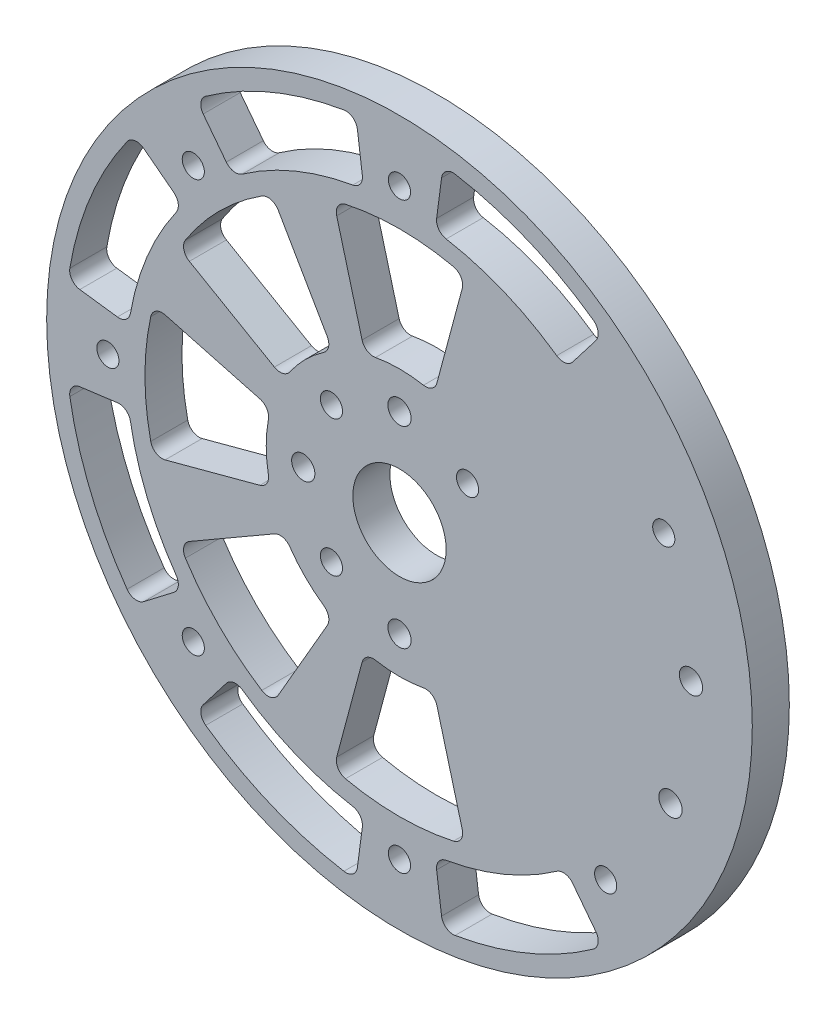
SolidWorks part; units mm, degrees
material "Balsa"
ref_plane "Front Plane" through (0, 0, 0) normal (0, 0, 1) x (1, 0, 0)
ref_plane "Top Plane" through (0, 0, 0) normal (0, 1, 0) x (1, 0, 0)
ref_plane "Right Plane" through (0, 0, 0) normal (1, 0, 0) x (0, 0, -1)
sketch "Sketch1" plane through (0, 0, 0) normal (0, 0, 1) x (1, 0, 0)
  line L0 (45.3154, 21.1309) -> (0, 0) construction
  line L1 (0, 0) -> (35.3553, -35.3553) construction
  line L2 (49.9788, 1.4542) -> (0, 0) construction
  line L3 (0, 0) -> (46.4674, -18.4603) construction
  circle A0 centre (45.3154, 21.1309) radius 1.8986
  circle A1 centre (49.9788, 1.4542) radius 1.9939
  circle A2 centre (0, 0) radius 60.5
  circle A3 centre (0, 0) radius 8
  circle A4 centre (0, 0) radius 16.5 construction
  circle A5 centre (46.4674, -18.4603) radius 1.9939
  circle A6 centre (0, 0) radius 50 construction
  circle A27 centre (0, -16.5) radius 1.9939
  circle A28 centre (11.6673, -11.6673) radius 1.8986 construction
  circle A30 centre (0, -50) radius 1.8986
  circle A31 centre (-16.5, 0) radius 1.9939
  circle A32 centre (-11.6673, -11.6673) radius 1.8986
  circle A33 centre (0, 16.5) radius 1.9939
  circle A34 centre (-11.6673, 11.6673) radius 1.8986
  circle A35 centre (16.5, 0) radius 1.9939 construction
  circle A36 centre (11.6673, 11.6673) radius 1.8986
  circle A38 centre (-35.3553, -35.3553) radius 1.8986
  circle A40 centre (-50, 0) radius 1.8986
  circle A42 centre (-35.3553, 35.3553) radius 1.8986
  circle A44 centre (0, 50) radius 1.8986
  circle A46 centre (35.3553, 35.3553) radius 1.8986 construction
  circle A48 centre (50, 0) radius 1.8986 construction
  circle A50 centre (35.3553, -35.3553) radius 1.8986
  dimension "D1" = 121
  dimension "D4" = 70
  dimension "D6" = 100
  dimension "D7" = 23.333
  dimension "D8" = 33
  dimension "D9" = 3.7973
  dimension "D10" = 3.9878
  dimension "D15" = 3.7973
  dimension "D17" = 3.9878
  dimension "D18" = 3.7973
  dimension "D3" = 16
  dimension "D11" = 3.9878
  dimension "D5" = 23.333
  dimension "D19" = 45
  dimension "D20" = 4
  dimension "D21" = 8
extrude "Boss-Extrude1" add sketch "Sketch1" along normal blind 6.35
sketch "Sketch2" plane through (0, 0, 6.35) normal (0, 0, 1) x (1, 0, 0)
  line L0 (0, 0) -> (-83.0843, 0) construction
  line L1 (-22.0714, 5.914) -> (-42.1627, 11.2975)
  line L2 (-22.0714, -5.914) -> (-42.1627, -11.2975)
  arc A0 (-42.1627, -11.2975) -> (-42.1627, 11.2975) centre (0, 0) cw
  arc A1 (-22.0714, -5.914) -> (-22.0714, 5.914) centre (0, 0) cw
  circle A2 centre (-16.5, 0) radius 1.9939 construction
  circle A3 centre (-50, 0) radius 1.8987 construction
  point P7 (-22.85, 0)
  point P10 (-43.65, 0)
  dimension "D2" = 6.35
  dimension "D3" = 6.35
  dimension "D1" = 30
extrude "Cut-Extrude1" cut sketch "Sketch2" against normal through all
fillet "Fillet1" radius 2 4 edges at (-42.1627, -11.2975, 3.175) (-22.0714, -5.914, 3.175) (-22.0714, 5.914, 3.175) (-42.1627, 11.2975, 3.175)
pattern_circular "CirPattern1" count 8 over 360 about axis through (0, 0, 6.35) along (0, 0, -1) skipping 3, 4, 5 of "Fillet1", "Cut-Extrude1"
sketch "Sketch3" plane through (0, 0, 6.35) normal (0, 0, 1) x (1, 0, 0)
  line L0 (-83.2273, 0) -> (0, 0) construction
  line L1 (0, 0) -> (-85.2421, 35.3084) construction
  line L2 (-45.479, 34.8972) -> (-37.1488, 28.5053)
  line L3 (-46.4244, 6.1119) -> (-56.8346, 7.4824)
  arc A0 (-56.8346, 7.4824) -> (-45.479, 34.8972) centre (0, 0) cw
  arc A1 (-46.4244, 6.1119) -> (-37.1488, 28.5053) centre (0, 0) cw
  circle A2 centre (-50, 0) radius 1.8987 construction
  circle A3 centre (-50, 0) radius 1.8986 construction
  circle A4 centre (0, 0) radius 60.5 construction
  arc A5 (-42.6565, 9.2598) -> (-42.6565, -9.2598) centre (0, 0) ccw construction
  point P12 (-43.2607, 17.9192)
  dimension "D3" = 3.175
  dimension "D4" = 3.175
  dimension "D1" = 22.5
  dimension "D2" = 30
extrude "Cut-Extrude2" cut sketch "Sketch3" against normal through all
fillet "Fillet2" radius 2 4 edges at (-56.8346, 7.4824, 3.175) (-46.4244, 6.1119, 3.175) (-37.1488, 28.5053, 3.175) (-45.479, 34.8972, 3.175)
pattern_circular "CirPattern3" count 8 over 360 about axis through (0, 0, 6.35) along (0, 0, -1) skipping 3, 4 of "Cut-Extrude2", "Fillet2"
sketch "Sketch4" plane through (0, 0, 0) normal (0, 0, -1) x (-1, 0, 0)
  circle A0 centre (0, 50) radius 1.8986 construction
  circle A1 centre (35.3553, 35.3553) radius 1.8987 construction
  circle A2 centre (50, 0) radius 1.8987 construction
  circle A3 centre (35.3553, -35.3553) radius 1.8987 construction
  circle A4 centre (0, -50) radius 1.8986 construction
  circle A5 centre (-35.3553, -35.3553) radius 1.8987 construction
  circle A6 centre (-45.3154, 21.1309) radius 1.8987 construction
  circle A7 centre (0, 50) radius 1.8986
  circle A8 centre (35.3553, 35.3553) radius 1.8986
  circle A9 centre (50, 0) radius 1.8986
  circle A10 centre (35.3553, -35.3553) radius 1.8986
  circle A11 centre (0, -50) radius 1.8986
  circle A12 centre (-35.3553, -35.3553) radius 1.8986
  circle A13 centre (-45.3154, 21.1309) radius 1.8986
  circle A14 centre (0, 50) radius 4.7625
  circle A15 centre (35.3553, 35.3553) radius 4.7625
  circle A16 centre (50, 0) radius 4.7625
  circle A17 centre (35.3553, -35.3553) radius 4.7625
  circle A18 centre (0, -50) radius 4.7625
  circle A19 centre (-35.3553, -35.3553) radius 4.7625
  circle A20 centre (-45.3154, 21.1309) radius 4.7625
  dimension "D1" = 9.525
extrude "Cut-Extrude3" cut sketch "Sketch4" against normal blind 3.5719
